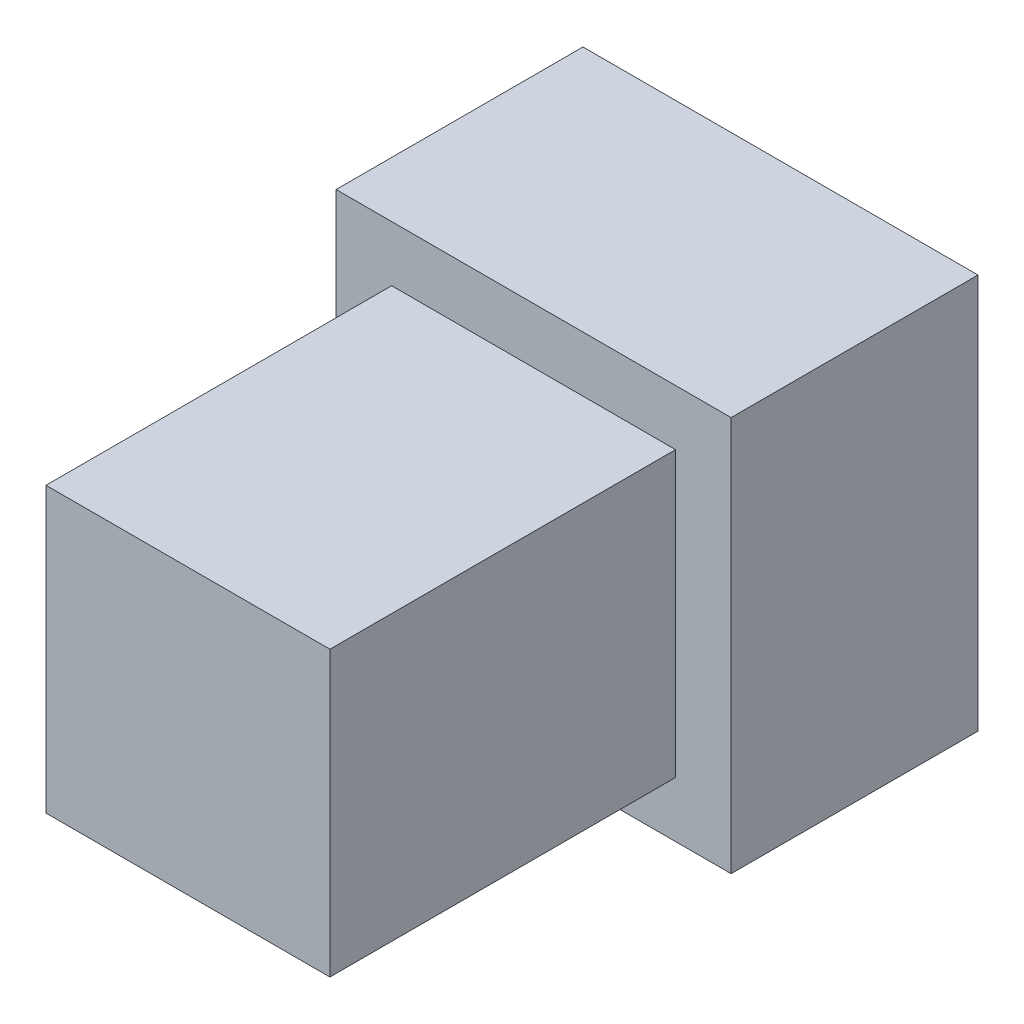
SolidWorks part; units mm, degrees
ref_plane "Front Plane" through (0, 0, 0) normal (0, 0, 1) x (1, 0, 0)
ref_plane "Top Plane" through (0, 0, 0) normal (0, 1, 0) x (1, 0, 0)
ref_plane "Right Plane" through (0, 0, 0) normal (1, 0, 0) x (0, 0, -1)
sketch "Sketch1" plane through (0, 0, 0) normal (0, 0, 1) x (1, 0, 0)
  line L1 (-4, -4) -> (4, -4)
  line L2 (-4, -4) -> (-4, 4)
  line L3 (-4, 4) -> (4, 4)
  line L4 (4, -4) -> (4, 4)
  line L5 (-4, -4) -> (4, 4) construction
  line L6 (-4, 4) -> (4, -4) construction
  point P0 (0, 0)
  dimension "D1" = 8
  dimension "D2" = 8
extrude "Boss-Extrude1" add sketch "Sketch1" along normal blind 5
sketch "Sketch3" plane through (0, 0, 5) normal (0, 0, 1) x (1, 0, 0)
  line L1 (-2.875, -2.875) -> (2.875, -2.875)
  line L2 (-2.875, -2.875) -> (-2.875, 2.875)
  line L3 (-2.875, 2.875) -> (2.875, 2.875)
  line L4 (2.875, -2.875) -> (2.875, 2.875)
  line L5 (-2.875, -2.875) -> (2.875, 2.875) construction
  line L6 (-2.875, 2.875) -> (2.875, -2.875) construction
  point P0 (0, 0)
  dimension "D1" = 5.75
  dimension "D2" = 5.75
extrude "Boss-Extrude2" add sketch "Sketch3" along normal blind 7
